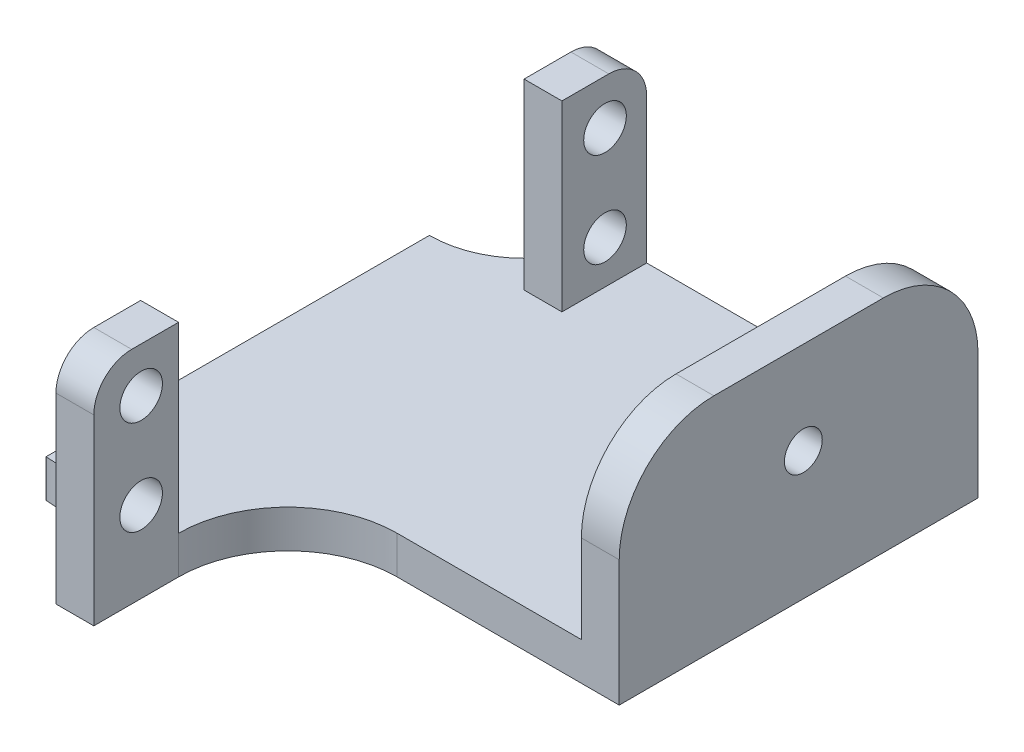
SolidWorks part; units mm, degrees
material "PLA"
ref_plane "Front Plane" through (0, 0, 0) normal (0, 0, 1) x (1, 0, 0)
ref_plane "Top Plane" through (0, 0, 0) normal (0, 1, 0) x (1, 0, 0)
ref_plane "Right Plane" through (0, 0, 0) normal (1, 0, 0) x (0, 0, -1)
sketch "Sketch1" plane through (0, 0, 0) normal (0, 1, 0) x (1, 0, 0)
  line L0 (-49, 49.45) -> (-39, 49.45)
  line L1 (-39, 49.45) -> (-39, 58.4)
  line L2 (-39, 58.4) -> (0, 58.4)
  line L3 (0, 58.4) -> (0, 0)
  line L4 (0, 0) -> (-39, 0)
  line L5 (-39, 0) -> (-39, 8.95)
  line L6 (-39, 8.95) -> (-49, 8.95)
  line L7 (-49, 8.95) -> (-49, 49.45)
  dimension "D1" = 58.4
  dimension "D2" = 49
  dimension "D3" = 10
  dimension "D4" = 8.95
  dimension "D5" = 8.95
extrude "Boss-Extrude1" add sketch "Sketch1" along normal blind 4
sketch "Sketch2" plane through (-39, 0, 0) normal (-1, 0, 0) x (0, 0, 1)
  line L0 (-58.4, 4) -> (-49.45, 4) construction
  line L1 (-8.95, 23.3) -> (0, 23.3)
  line L2 (-8.95, 23.3) -> (-8.95, 4)
  line L3 (-8.95, 4) -> (0, 4)
  line L4 (0, 23.3) -> (0, 4)
  line L5 (-58.4, 23.3) -> (-49.45, 23.3)
  line L6 (-58.4, 23.3) -> (-58.4, 4)
  line L7 (-58.4, 4) -> (-49.45, 4)
  line L8 (-49.45, 23.3) -> (-49.45, 4)
  line L9 (-58.4, 4) -> (-58.4, 0) construction
  line L10 (-49.45, 4) -> (-49.45, 0) construction
  line L11 (-8.95, 4) -> (0, 4) construction
  line L12 (0, 4) -> (0, 0) construction
  line L13 (-8.95, 4) -> (-8.95, 0) construction
  line L14 (-49.45, 4) -> (-8.95, 4) construction
  circle A0 centre (-5, 18.55) radius 2.25
  circle A1 centre (-5, 8.55) radius 2.25
  circle A2 centre (-54, 18.55) radius 2.25
  circle A3 centre (-54, 8.55) radius 2.25
  dimension "D1" = 4.5
  dimension "D2" = 4.5
  dimension "D8" = 4.5
  dimension "D9" = 4.5
  dimension "D3" = 19.3
  dimension "D4" = 10
  dimension "D5" = 4.55
  dimension "D6" = 4.55
  dimension "D7" = 4.55
  dimension "D10" = 3.95
extrude "Boss-Extrude2" add sketch "Sketch2" against normal blind 4
fillet "Fillet1" radius 10 2 edges at (-39, 2, -49.45) (-39, 2, -8.95)
fillet "Fillet2" radius 4 2 edges at (-37, 23.3, -58.4) (-37, 23.3, 0)
sketch "Sketch3" plane through (0, 0, 0) normal (1, 0, 0) x (0, 0, -1)
  line L0 (0, 4) -> (58.4, 4) construction
  line L1 (0, 23.3) -> (58.4, 23.3)
  line L2 (0, 23.3) -> (0, 4)
  line L3 (0, 4) -> (58.4, 4)
  line L4 (58.4, 23.3) -> (58.4, 4)
  line L5 (0, 4) -> (0, 0) construction
  line L6 (58.4, 4) -> (58.4, 0) construction
  circle A0 centre (39.95, 13.55) radius 2
  dimension "D4" = 4
  dimension "D1" = 19.3
  dimension "D2" = 18.45
  dimension "D3" = 9.55
extrude "Boss-Extrude3" add sketch "Sketch3" against normal blind 4
sketch "Sketch4" plane through (0, 0, 0) normal (0, -1, 0) x (1, 0, 0)
  line L0 (0, 0) -> (0, -20.5)
  line L1 (0, 0) -> (0, -58.4) construction
  line L2 (0, -20.5) -> (-23.45, -20.5)
  line L3 (0, 0) -> (-35, 0)
  line L4 (-39, 0) -> (0, 0) construction
  line L5 (-35, 0) -> (-35, -8.95)
  arc A0 (-35, -8.95) -> (-23.45, -20.5) centre (-23.45, -8.95) ccw
  dimension "D1" = 20.5
  dimension "D2" = 35
  dimension "D3" = 23.45
  dimension "D4" = 8.95
extrude "Cut-Extrude1" cut sketch "Sketch4" against normal up to next
fillet "Fillet3" radius 10 2 edges at (-2, 23.3, -20.5) (-2, 23.3, -58.4)
